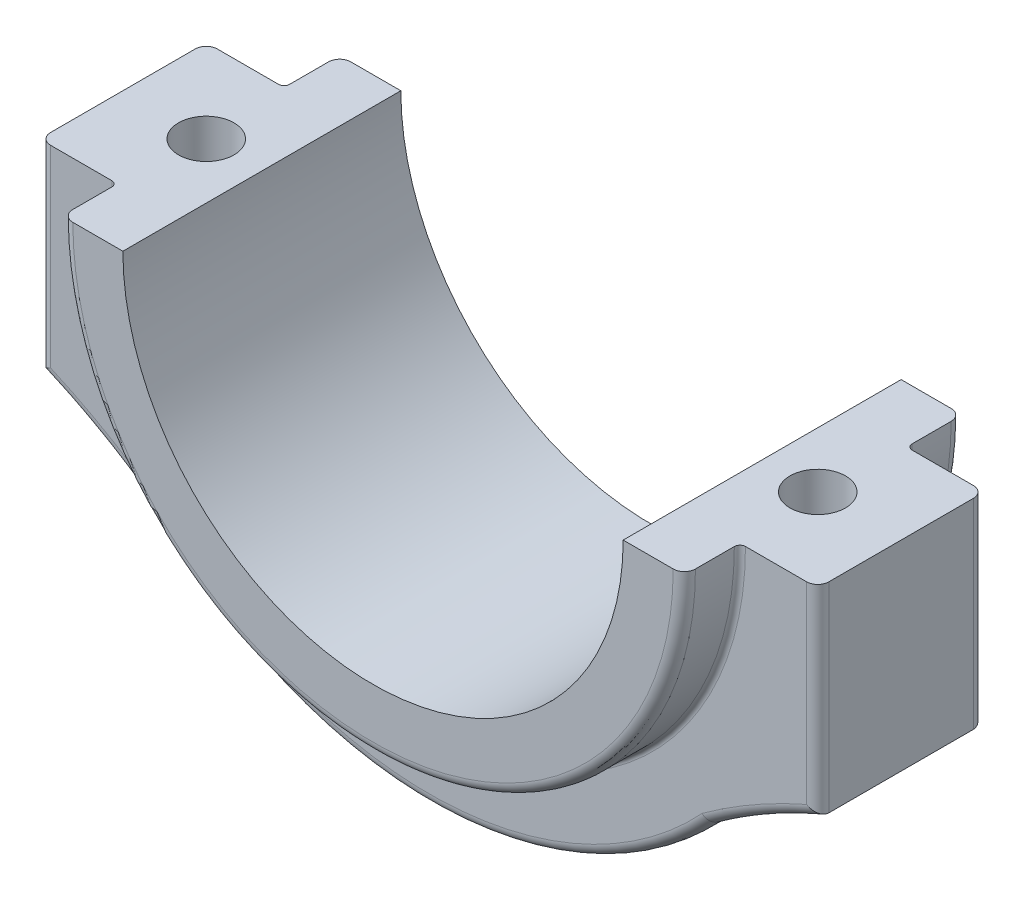
SolidWorks part; units mm, degrees
material "A286 Súper aleación a base de hierro"
ref_plane "Alzado" through (0, 0, 0) normal (0, 0, 1) x (1, 0, 0)
ref_plane "Planta" through (0, 0, 0) normal (0, 1, 0) x (1, 0, 0)
ref_plane "Vista lateral" through (0, 0, 0) normal (1, 0, 0) x (0, 0, -1)
sketch "Croquis1" plane through (0, 0, 0) normal (0, 0, 1) x (1, 0, 0)
  line L0 (22.5, 0) -> (28, 0)
  line L2 (-22.5, 0) -> (-28, 0)
  arc A0 (-22.5, 0) -> (22.5, 0) centre (0, 0) ccw
  arc A1 (-28, 0) -> (28, 0) centre (0, 0) ccw
  dimension "D1" = 28
  dimension "D2" = 22.5
  dimension "D3" = 22.5
extrude "Saliente-Extruir1" add sketch "Croquis1" along normal mid plane 25
sketch "Croquis3" plane through (0, 0, 0) normal (0, 0, 1) x (1, 0, 0)
  line L0 (-35, 0) -> (-22.5, 0)
  line L1 (-35, 0) -> (-35, -18)
  line L3 (0, -22.5) -> (0, -34.5)
  arc A0 (-25.2669, -23.4912) -> (0, -34.5) centre (0, 0) ccw
  arc A1 (-35, -18) -> (-25.2669, -23.4912) centre (-54.548, -64.0204) cw
  arc A2 (-22.5, 0) -> (0, -22.5) centre (0, 0) ccw
  dimension "D2" = 69
  dimension "D3" = 18
extrude "Saliente-Extruir2" add sketch "Croquis3" along normal mid plane 15
mirror "Simetría1" about plane through (0, 0, 0) normal (1, 0, 0) of "Saliente-Extruir2"
ref_plane "Plano1" through (0, -18, 0) normal (0, 1, 0) x (1, 0, 0)
sketch "Croquis4" plane through (0, -18, 0) normal (0, 1, 0) x (1, 0, 0)
  circle A0 centre (-27.5, 0) radius 6.5
  dimension "D2" = 13
extrude "Cortar-Extruir1" cut sketch "Croquis4" against normal blind 15
sketch "Croquis5" plane through (0, -18, 0) normal (0, 1, 0) x (1, 0, 0)
  circle A0 centre (-27.5, 0) radius 2.5
  dimension "D2" = 5
extrude "Cortar-Extruir4" cut sketch "Croquis5" along normal up to next
mirror "Simetría2" about plane through (0, 0, 0) normal (1, 0, 0) of "Cortar-Extruir1", "Cortar-Extruir4"
fillet "Redondeo1" radius 1 10 edges at (29.9795, -20.4728, 7.5) (29.9795, -20.4728, -7.5) (35, -9, 7.5) (35, -9, -7.5) (-29.9795, -20.4728, 7.5) (-35, -9, 7.5) (-29.9795, -20.4728, -7.5) (-35, -9, -7.5) (0, -28, 12.5) (0, -28, -12.5)
fillet "Redondeo2" radius 0.5 2 edges at (0, -28, -7.5) (0, -28, 7.5)
fillet "Redondeo3" radius 1 2 edges at (0, -34.5, 7.5) (0, -34.5, -7.5)
